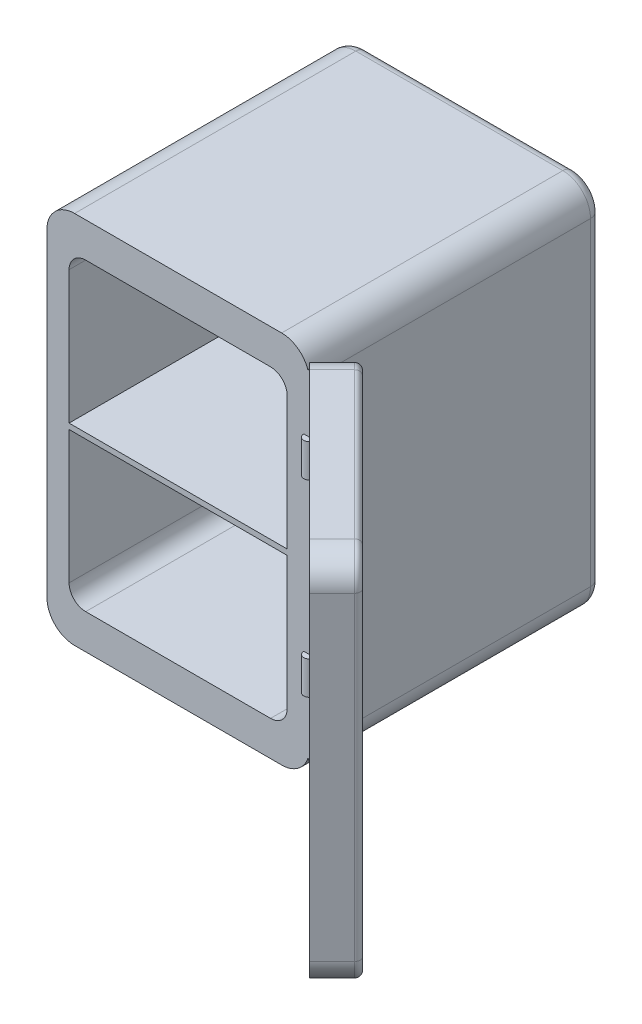
SolidWorks part; units mm, degrees
ref_plane "前视基准面" through (0, 0, 0) normal (0, 0, 1) x (1, 0, 0)
ref_plane "上视基准面" through (0, 0, 0) normal (0, 1, 0) x (1, 0, 0)
ref_plane "右视基准面" through (0, 0, 0) normal (1, 0, 0) x (0, 0, -1)
sketch "草图1" plane through (0, 0, 0) normal (0, 0, 1) x (1, 0, 0)
  line L1 (-118.5, -169) -> (118.5, -169)
  line L2 (-118.5, -169) -> (-118.5, 169)
  line L3 (-118.5, 169) -> (118.5, 169)
  line L4 (118.5, -169) -> (118.5, 169)
  line L5 (-118.5, -169) -> (118.5, 169) construction
  line L6 (-118.5, 169) -> (118.5, -169) construction
  point P0 (0, 0)
  dimension "D1" = 237
  dimension "D2" = 338
extrude "凸台-拉伸1" add sketch "草图1" against normal blind 264
sketch "草图2" plane through (0, 0, 0) normal (0, 0, 1) x (1, 0, 0)
  line L0 (-118.5, 169) -> (-118.5, -169) construction
  line L1 (-98.5, 137.5) -> (98.5, 137.5)
  line L2 (-98.5, 137.5) -> (-98.5, -137.5)
  line L3 (-98.5, -137.5) -> (98.5, -137.5)
  line L4 (98.5, 137.5) -> (98.5, -137.5)
  line L5 (-98.5, 137.5) -> (98.5, -137.5) construction
  line L6 (-98.5, -137.5) -> (98.5, 137.5) construction
  point P0 (0, 0)
  dimension "D1" = 275
  dimension "D2" = 20
extrude "切除-拉伸1" cut sketch "草图2" against normal blind 248
sketch "草图3" plane through (0, 0, 0) normal (0, 0, 1) x (1, 0, 0)
  line L0 (118.5, -169) -> (118.5, 169) construction
  line L1 (-118.5, -2.5) -> (118.5, -2.5)
  line L2 (-118.5, -2.5) -> (-118.5, 2.5)
  line L3 (-118.5, 2.5) -> (118.5, 2.5)
  line L4 (118.5, -2.5) -> (118.5, 2.5)
  line L5 (-118.5, -2.5) -> (118.5, 2.5) construction
  line L6 (-118.5, 2.5) -> (118.5, -2.5) construction
  point P0 (0, 0)
  dimension "D1" = 5
extrude "凸台-拉伸2" add sketch "草图3" against normal blind 255
sketch "草图4" plane through (0, 0, 0) normal (0, 1, 0) x (1, 0, 0)
  circle A0 centre (118.5, 0) radius 5
  dimension "D1" = 10
extrude "凸台-拉伸3" add sketch "草图4" along normal blind 30 from offset 70
mirror "镜向1" about plane through (0, 0, 0) normal (0, 1, 0) of "凸台-拉伸3"
ref_plane "基准面1" through (59.25, 0, -59.25) normal (-0.7071, 0, 0.7071) x (0, 1, 0)
sketch "草图6" plane through (59.25, 0, -59.25) normal (-0.7071, 0, 0.7071) x (0, 1, 0)
  line L1 (169, -318.7922) -> (-169, -318.7922)
  line L2 (169, -318.7922) -> (169, -81.7922)
  line L3 (169, -81.7922) -> (-169, -81.7922)
  line L4 (-169, -318.7922) -> (-169, -81.7922)
  line L5 (169, -318.7922) -> (-169, -81.7922) construction
  line L6 (169, -81.7922) -> (-169, -318.7922) construction
  line L7 (-169, 83.7922) -> (-169, -83.7922) construction
  line L8 (-169, -83.7922) -> (-100, -83.7922) construction
  point P0 (0, -200.2922)
  dimension "D1" = 237
  dimension "D2" = 338
  dimension "D3" = 0
  dimension "D4" = 2
extrude "凸台-拉伸6" add sketch "草图6" against normal blind 34
fillet "圆角1" radius 25 8 edges at (118.5, -169, -133.4142) (-118.5, -169, -132) (129.8137, -169, -14.1421) (296.6909, -169, 154.1493) (296.6909, 169, 154.1493) (129.8137, 169, -14.1421) (118.5, 169, -133.4142) (-118.5, 169, -132)
fillet "圆角2" radius 10 8 edges at (111.1777, -161.6777, -264) (0, -169, -264) (-111.1777, -161.6777, -264) (-118.5, 0, -264) (-111.1777, 161.6777, -264) (0, 169, -264) (111.1777, 161.6777, -264) (118.5, 0, -264)
fillet "圆角3" radius 5 8 edges at (303.5341, -161.6777, 136.9508) (224.9196, -169, 58.3363) (146.3051, -161.6777, -20.2782) (141.1274, 0, -25.4558) (146.3051, 161.6777, -20.2782) (224.9196, 169, 58.3363) (303.5341, 161.6777, 136.9508) (308.7117, 0, 142.1285)
fillet "圆角4" radius 15 6 edges at (98.5, 137.5, -124) (0, -137.5, -248) (98.5, -137.5, -124) (-98.5, -137.5, -124) (0, 137.5, -248) (-98.5, 137.5, -124)
fillet "圆角5" radius 15 4 edges at (94.1066, 133.1066, -243.6066) (-94.1066, 133.1066, -243.6066) (98.5, 62.5, -248) (-98.5, 62.5, -248)
